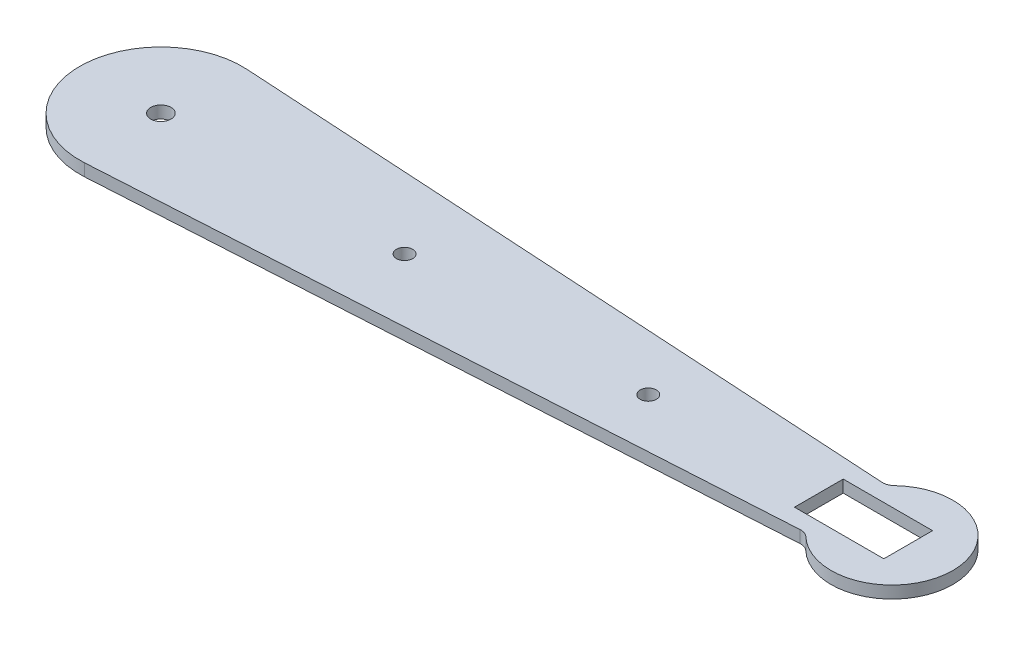
SolidWorks part; units mm, degrees
ref_plane "Front Plane" through (0, 0, 0) normal (0, 0, 1) x (1, 0, 0)
ref_plane "Top Plane" through (0, 0, 0) normal (0, 1, 0) x (1, 0, 0)
ref_plane "Right Plane" through (0, 0, 0) normal (1, 0, 0) x (0, 0, -1)
sketch "Sketch1" plane through (0, 0, 0) normal (0, 1, 0) x (1, 0, 0)
  line L0 (0, 0) -> (180, 0) construction
  line L1 (168.8197, 10) -> (1.1868, 19.9648)
  line L2 (168.8197, -10) -> (1.1868, -19.9648)
  circle A0 centre (0, 0) radius 20
  circle A1 centre (180, 0) radius 15
  circle A2 centre (0, 0) radius 2.5
  circle A4 centre (60, 0) radius 2
  circle A5 centre (120, 0) radius 2
  dimension "D1" = 40
  dimension "D2" = 30
  dimension "D6" = 60
  dimension "D8" = 5
  dimension "D9" = 4
  dimension "D10" = 4
  dimension "D3" = 180
  dimension "D4" = 10
  dimension "D5" = 10
  dimension "D7" = 120
extrude "Boss-Extrude1" add sketch "Sketch1" along normal blind 3 contours A2 A0 | A0 L0 A4 A5 A1 L1 | L0 A0 L2 A1 A5 A4 | A1 region at (14.144, 0, 13.3282) region at (83.3917, 0, -7.7749) region at (83.3917, 0, 7.7749) region at (185.2009, 0, -13.6162)
fillet "Fillet2" radius 3 1 edges at (168.8197, 1.5, -10) type face fillet first side face at (85.0032, 1.5, -14.9824) second side face at (181.9098, 1.5, 0)
fillet "Fillet3" radius 3 1 edges at (168.8197, 1.5, 10) type face fillet first side face at (85.0032, 1.5, 14.9824) second side face at (182.1213, 1.5, 0.0885)
sketch "Sketch2" plane through (0, 3, 0) normal (0, 1, 0) x (1, 0, 0)
  line L1 (162, 6) -> (184, 6)
  line L2 (162, 6) -> (162, -6)
  line L3 (162, -6) -> (184, -6)
  line L4 (184, 6) -> (184, -6)
  arc A0 (169.6916, -10.8967) -> (169.6916, 10.8967) centre (180, 0) ccw construction
  point P7 (195, 0)
  dimension "D1" = 12
  dimension "D2" = 22
  dimension "D3" = 6
  dimension "D5" = 4
extrude "Cut-Extrude1" cut sketch "Sketch2" against normal blind 10
